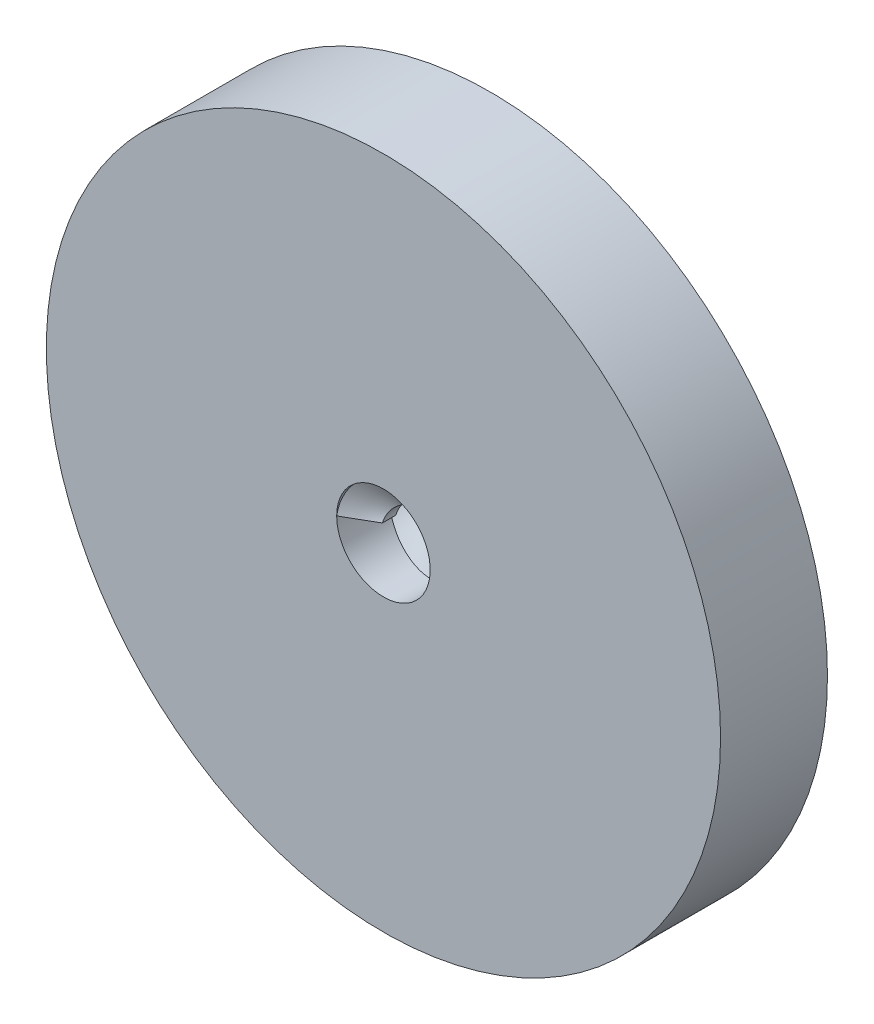
SolidWorks part; units mm, degrees
material "Nailon 101"
ref_plane "Alzado" through (0, 0, 0) normal (0, 0, 1) x (1, 0, 0)
ref_plane "Planta" through (0, 0, 0) normal (0, 1, 0) x (1, 0, 0)
ref_plane "Vista lateral" through (0, 0, 0) normal (1, 0, 0) x (0, 0, -1)
sketch "Croquis1" plane through (0, 0, 0) normal (0, 0, 1) x (1, 0, 0)
  circle A0 centre (0, 0) radius 25.225
  dimension "D1" = 50.45
extrude "Saliente-Extruir1" add sketch "Croquis1" along normal blind 8
sketch "Croquis2" plane through (0, 0, 8) normal (0, 0, 1) x (1, 0, 0)
  circle A0 centre (0, 0) radius 0.5
  dimension "D1" = 1
sketch "Croquis8" plane through (0, 0, 8) normal (0, 0, 1) x (1, 0, 0)
  circle A0 centre (0, 0) radius 3.5
  dimension "D1" = 7
extrude "Cortar-Extruir1" cut sketch "Croquis8" against normal blind 8
thread "Rosca1" pitch 4 method extrude profile "Perfil de rosca2" start angle 0, offset 0, length 8, pitch 4, diameter 7
ref_plane "Plano2" through (-3.5, 0, 8) normal (0, -1, 0) x (-1, 0, 0)
sketch "Perfil de rosca2" plane through (-3.5, 0, 8) normal (0, -1, 0) x (-1, 0, 0)
  line L0 (0, 0) -> (0, 4) construction
  line L11 (0, 0) -> (0, 3.5)
  line L12 (0, 3.5) -> (-2.1651, 2.25)
  line L13 (-2.1651, 2.25) -> (-2.1651, 1.25)
  line L15 (-2.1651, 1.25) -> (0, 0)
  line L17 (-2.1651, 1.75) -> (0, 1.75) construction
  point P2 (0, 0)
  dimension "Pitch" = 4
  dimension "Profile_Angle" = 60
  dimension "Profile_Land" = 1
  dimension "Profile_Height" = 2.1651
sketch "Croquis11" plane through (0, 0, 0) normal (0, 1, 0) x (1, 0, 0)
  line L0 (-4.0325, 0) -> (5.1061, 0)
  line L1 (25.225, 0) -> (-25.225, 0) construction
  line L2 (5.1061, 0) -> (5.1061, 6.0215)
  line L3 (5.1061, 6.0215) -> (-4.0325, 6.0215)
  line L4 (-4.0325, 6.0215) -> (-4.0325, 0)
extrude "Cortar-Extruir2" cut sketch "Croquis11" against normal through all both and the other way through all
